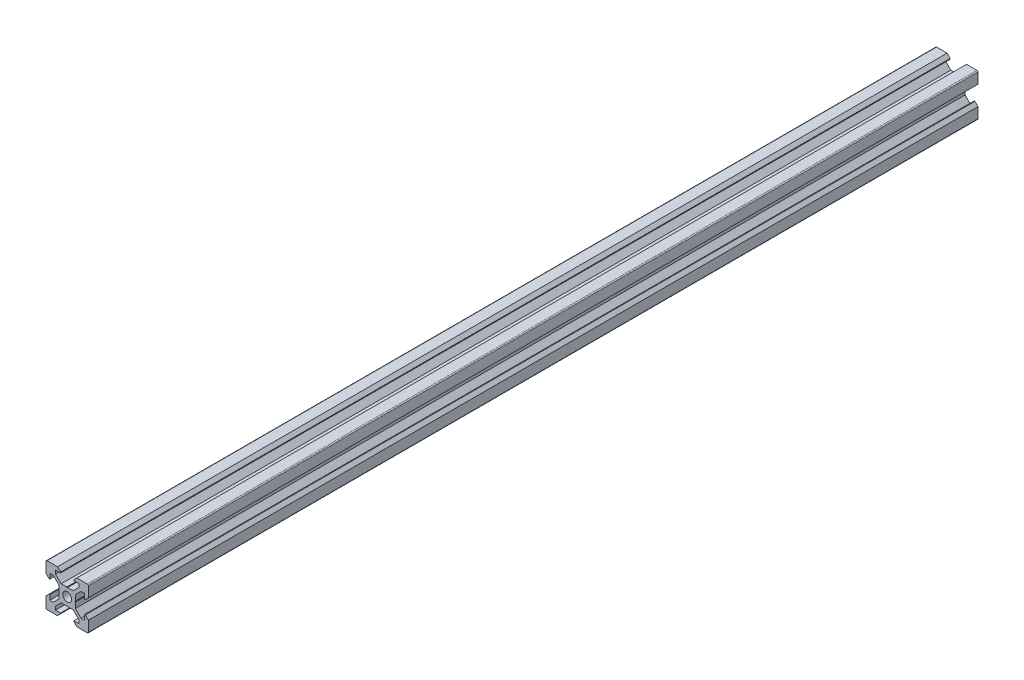
SolidWorks part; units mm, degrees
material "6061-T6 (SS)"
ref_plane "Front Plane" through (0, 0, 0) normal (0, 0, 1) x (1, 0, 0)
ref_plane "Top Plane" through (0, 0, 0) normal (0, 1, 0) x (1, 0, 0)
ref_plane "Right Plane" through (0, 0, 0) normal (1, 0, 0) x (0, 0, -1)
sketch "Sketch1" plane through (0, 0, 0) normal (0, 0, 1) x (1, 0, 0)
  line L1 (9.5, -10) -> (-9.5, -10)
  line L2 (10, -9.5) -> (10, 9.5)
  line L3 (9.5, 10) -> (-9.5, 10)
  line L4 (-10, -9.5) -> (-10, 9.5)
  line L5 (10, -10) -> (-10, 10) construction
  line L6 (10, 10) -> (-10, -10) construction
  circle A0 centre (0, 0) radius 2.1
  arc A1 (-9.5, 10) -> (-10, 9.5) centre (-9.5, 9.5) ccw
  arc A2 (10, 9.5) -> (9.5, 10) centre (9.5, 9.5) ccw
  arc A3 (9.5, -10) -> (10, -9.5) centre (9.5, -9.5) ccw
  arc A4 (-9.5, -10) -> (-10, -9.5) centre (-9.5, -9.5) cw
  point P0 (0, 0)
  line B0 (0, 0) -> (0, 10) construction
  line B1 (0, 3.69) -> (-0.21, 3.9)
  line B2 (-0.21, 3.9) -> (-2.8393, 3.9)
  line B3 (-2.8393, 3.9) -> (-5.5, 6.5607)
  line B4 (-5.5, 6.5607) -> (-5.5, 8.2)
  line B5 (-5.5, 8.2) -> (-3.125, 8.2)
  line B6 (-3.125, 8.2) -> (-3.125, 8.545)
  line B7 (-3.125, 8.545) -> (-4.58, 10)
  line B8 (-4.58, 10) -> (4.58, 10)
  line B9 (0, 0) -> (-5.9132, 5.9132) construction
  line B10 (3.125, 8.545) -> (4.58, 10)
  line B11 (3.125, 8.2) -> (3.125, 8.545)
  line B12 (5.5, 8.2) -> (3.125, 8.2)
  line B13 (5.5, 6.5607) -> (5.5, 8.2)
  line B14 (2.8393, 3.9) -> (5.5, 6.5607)
  line B15 (0.21, 3.9) -> (2.8393, 3.9)
  line B16 (0, 3.69) -> (0.21, 3.9)
  line B17 (0, 0) -> (-10, 0) construction
  line B18 (-3.69, 0) -> (-3.9, -0.21)
  line B19 (-3.9, -0.21) -> (-3.9, -2.8393)
  line B20 (-3.9, -2.8393) -> (-6.5607, -5.5)
  line B21 (-6.5607, -5.5) -> (-8.2, -5.5)
  line B22 (-8.2, -5.5) -> (-8.2, -3.125)
  line B23 (-8.2, -3.125) -> (-8.545, -3.125)
  line B24 (-8.545, -3.125) -> (-10, -4.58)
  line B25 (-10, -4.58) -> (-10, 4.58)
  line B26 (0, 0) -> (-5.9132, -5.9132) construction
  line B27 (-8.545, 3.125) -> (-10, 4.58)
  line B28 (-8.2, 3.125) -> (-8.545, 3.125)
  line B29 (-8.2, 5.5) -> (-8.2, 3.125)
  line B30 (-6.5607, 5.5) -> (-8.2, 5.5)
  line B31 (-3.9, 2.8393) -> (-6.5607, 5.5)
  line B32 (-3.9, 0.21) -> (-3.9, 2.8393)
  line B33 (-3.69, 0) -> (-3.9, 0.21)
  line B34 (0, 0) -> (0, -10) construction
  line B35 (0, -3.69) -> (0.21, -3.9)
  line B36 (0.21, -3.9) -> (2.8393, -3.9)
  line B37 (2.8393, -3.9) -> (5.5, -6.5607)
  line B38 (5.5, -6.5607) -> (5.5, -8.2)
  line B39 (5.5, -8.2) -> (3.125, -8.2)
  line B40 (3.125, -8.2) -> (3.125, -8.545)
  line B41 (3.125, -8.545) -> (4.58, -10)
  line B42 (4.58, -10) -> (-4.58, -10)
  line B43 (0, 0) -> (5.9132, -5.9132) construction
  line B44 (-3.125, -8.545) -> (-4.58, -10)
  line B45 (-3.125, -8.2) -> (-3.125, -8.545)
  line B46 (-5.5, -8.2) -> (-3.125, -8.2)
  line B47 (-5.5, -6.5607) -> (-5.5, -8.2)
  line B48 (-2.8393, -3.9) -> (-5.5, -6.5607)
  line B49 (-0.21, -3.9) -> (-2.8393, -3.9)
  line B50 (0, -3.69) -> (-0.21, -3.9)
  line B51 (0, 0) -> (10, 0) construction
  line B52 (3.69, 0) -> (3.9, 0.21)
  line B53 (3.9, 0.21) -> (3.9, 2.8393)
  line B54 (3.9, 2.8393) -> (6.5607, 5.5)
  line B55 (6.5607, 5.5) -> (8.2, 5.5)
  line B56 (8.2, 5.5) -> (8.2, 3.125)
  line B57 (8.2, 3.125) -> (8.545, 3.125)
  line B58 (8.545, 3.125) -> (10, 4.58)
  line B59 (10, 4.58) -> (10, -4.58)
  line B60 (0, 0) -> (5.9132, 5.9132) construction
  line B61 (8.545, -3.125) -> (10, -4.58)
  line B62 (8.2, -3.125) -> (8.545, -3.125)
  line B63 (8.2, -5.5) -> (8.2, -3.125)
  line B64 (6.5607, -5.5) -> (8.2, -5.5)
  line B65 (3.9, -2.8393) -> (6.5607, -5.5)
  line B66 (3.9, -0.21) -> (3.9, -2.8393)
  line B67 (3.69, 0) -> (3.9, -0.21)
  dimension "D1" = 4.2
  dimension "D3" = 0.5
  dimension "D2" = 20
sketch_block_instance "V Slot 1-4"
sketch_block "V Slot 1" parameters "D1"=10, "D2"=11, "D3"=4.3, "D4"=1.8, "D5"=0.21, "D6"=45, "D7"=9.16, "D8"=1.5, "D9"=6.25
sketch_block_instance "V Slot 1-5"
sketch_block_instance "V Slot 1-6"
sketch_block_instance "V Slot 1-7"
extrude "Boss-Extrude1" add sketch "Sketch1" along normal mid plane 420 contours B67 B52 B53 B54 B55 B56 B57 B58 L2 A2 L3 B10 B11 B12 B13 B14 B15 B16 B1 B2 B3 B4 B5 B6 B7 A1 L4 B27 B28 B29 B30 B31 B32 B33 B18 B19 B20 B21 B22 B23 B24 A4 L1 B44 B45 B46 B47 B48 B49 region at (7.04, -9.7172, 0)
